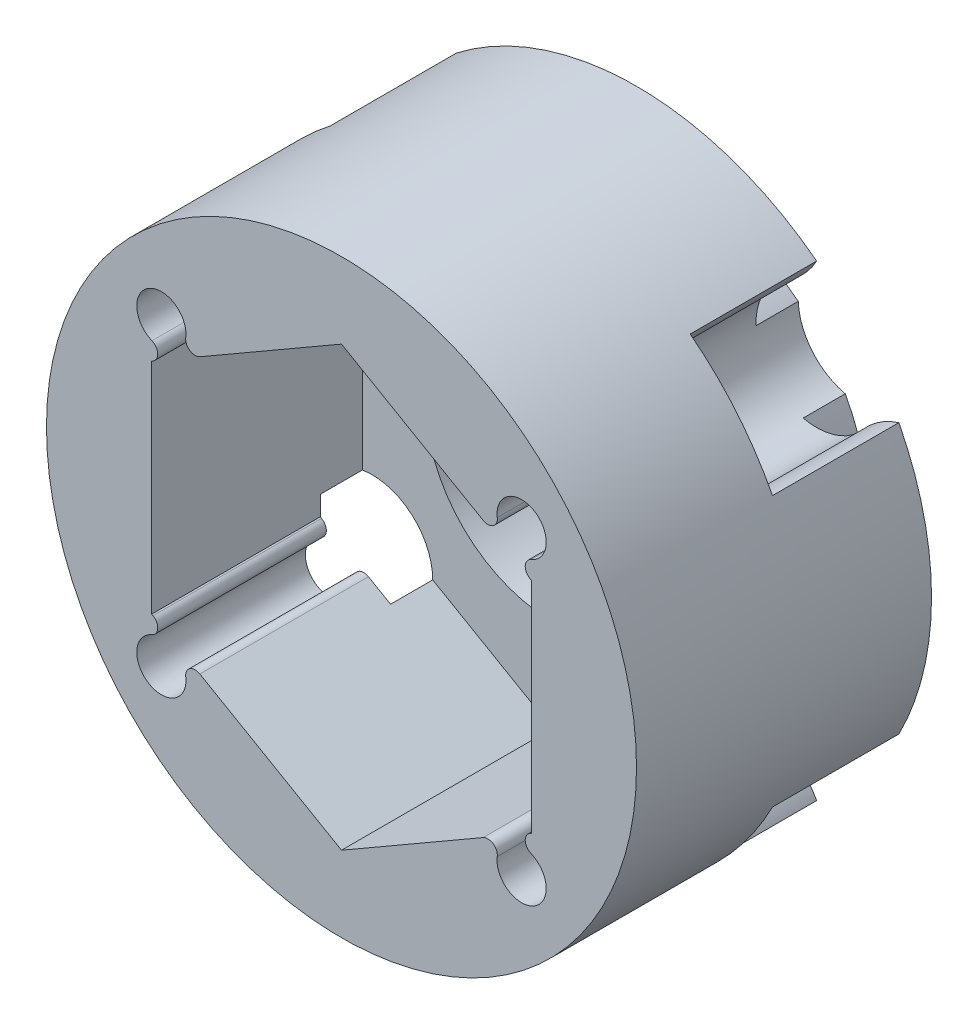
SolidWorks part; units mm, degrees
note: The reader was unsure of these and kept them because the rebuilt part matched: shared geometry of "Sketch4<3>", "Sketch1<5>", "Sketch1<6>", "Sketch4<4>".
material "ABS"
ref_plane "Front Plane" through (0, 0, 0) normal (0, 0, 1) x (1, 0, 0)
ref_plane "Top Plane" through (0, 0, 0) normal (0, 1, 0) x (1, 0, 0)
ref_plane "Right Plane" through (0, 0, 0) normal (1, 0, 0) x (0, 0, -1)
sketch "Sketch1" plane through (0, 0, 0) normal (0, 0, 1) x (1, 0, 0)
  line L0 (0, 8.7454) -> (0, -8.8136) construction
  line L1 (0, -5.2) -> (4.5033, -2.6)
  line L2 (4.5033, -2.6) -> (4.5033, 2.6)
  line L3 (4.5033, 2.6) -> (0, 5.2)
  line L4 (0, 5.2) -> (-4.5033, 2.6)
  line L5 (-4.5033, 2.6) -> (-4.5033, -2.6)
  line L6 (-4.5033, -2.6) -> (0, -5.2)
  line L7 (-10.713, 0) -> (12.0511, 0) construction
  line L8 (0, 0) -> (4.2741, -3.5588) construction
  circle A0 centre (0, 0) radius 7
  circle A1 centre (0, 0) radius 4.5033 construction
  arc A2 (4.4979, 3.0201) -> (3.6956, 3.4833) centre (4.2741, 3.5588) ccw
  arc A3 (3.6956, 3.4833) -> (3.3606, 3.2597) centre (3.4729, 3.4542) cw
  arc A4 (4.4979, 3.0201) -> (4.4718, 2.6182) centre (4.5841, 2.8127) ccw
  arc A5 (-4.4979, 3.0201) -> (-4.4718, 2.6182) centre (-4.5841, 2.8127) cw
  arc A6 (-3.6956, 3.4833) -> (-3.3606, 3.2597) centre (-3.4729, 3.4542) ccw
  arc A7 (-4.4979, 3.0201) -> (-3.6956, 3.4833) centre (-4.2741, 3.5588) cw
  arc A8 (4.4979, -3.0201) -> (4.4718, -2.6182) centre (4.5841, -2.8127) cw
  arc A9 (4.4979, -3.0201) -> (3.6956, -3.4833) centre (4.2741, -3.5588) cw
  arc A10 (3.6956, -3.4833) -> (3.3606, -3.2597) centre (3.4729, -3.4542) ccw
  arc A11 (-3.6956, -3.4833) -> (-3.3606, -3.2597) centre (-3.4729, -3.4542) cw
  arc A12 (-4.4979, -3.0201) -> (-4.4718, -2.6182) centre (-4.5841, -2.8127) ccw
  arc A13 (-4.4979, -3.0201) -> (-3.6956, -3.4833) centre (-4.2741, -3.5588) ccw
  dimension "D2" = 14
  dimension "D1" = 5.2
  dimension "D3" = 3.5588
extrude "Boss-Extrude1" add sketch "Sketch1" against normal blind 7 contours A0 A13 A12 L6 L5 L4 A5 A7 A6 L3 A3 A2 A4 L2 L1 A8 A9 A10 A11 | L5 L6 L1 L2 L3 L4 | A4 A2 A3 L3 | A12 A13 A11 L6 | A10 A9 A8 L1 | A7 A5 L4 A6
sketch "Sketch4" plane through (0, 0, -7) normal (0, 0, -1) x (-1, 0, 0)
  line L0 (0, 8.7454) -> (0, -8.8136) construction
  line L1 (0, 8.7454) -> (0, -8.8136)
  line L2 (10.713, 0) -> (-12.0511, 0) construction
  line L3 (10.713, 0) -> (-12.0511, 0)
  line L4 (-4.2741, 3.5588) -> (-6.1407, 5.113) construction
  circle A0 centre (-4.2741, 3.5588) radius 1.4383
  circle A1 centre (0, 0) radius 7 construction
  circle A2 centre (4.2741, 3.5588) radius 1.4383
  circle A3 centre (4.2741, -3.5588) radius 1.4383
  circle A4 centre (-4.2741, -3.5588) radius 1.4383
  arc A5 (-3.5838, 4.8206) -> (-4.2741, 5.5437) centre (-2.6179, 6.4337) cw
  arc A6 (-5.39, 2.6514) -> (-6.2261, 3.1993) centre (-6.8015, 1.4094) ccw
  arc A7 (5.39, 2.6514) -> (6.2261, 3.1993) centre (6.8015, 1.4094) cw
  arc A8 (3.5838, 4.8206) -> (4.2741, 5.5437) centre (2.6179, 6.4337) ccw
  arc A9 (5.39, -2.6514) -> (6.2261, -3.1993) centre (6.8015, -1.4094) ccw
  arc A10 (3.5838, -4.8206) -> (4.2741, -5.5437) centre (2.6179, -6.4337) cw
  arc A11 (-5.39, -2.6514) -> (-6.2261, -3.1993) centre (-6.8015, -1.4094) cw
  arc A12 (-3.5838, -4.8206) -> (-4.2741, -5.5437) centre (-2.6179, -6.4337) ccw
  circle A13 centre (0, 0) radius 3
  circle A14 centre (0, 0) radius 4.5033
  dimension "D1" = 6
extrude "Boss-Extrude2" add sketch "Sketch4" along normal blind 1 contours L3 A14 A4 L1 A13 | L1 A14 A0 L3 A13 | L3 A14 A2 L1 A13 | L1 A14 A3 L3 A13
extrude "Cut-Extrude4" cut sketch "Sketch4<3>" against normal blind 3
sketch "Sketch4<3>" plane through (0, 0, -7) normal (0, 0, -1) x (-1, 0, 0) same geometry as "Sketch4"
extrude "Cut-Extrude5" cut sketch "Sketch1<5>" against normal blind 5 contours L5 L6 L1 L2 L3 L4
sketch "Sketch1<5>" plane through (0, 0, 0) normal (0, 0, 1) x (1, 0, 0) same geometry as "Sketch1"
extrude "Cut-Extrude6" cut sketch "Sketch1<6>" against normal blind 5 contours A12 A13 A11 L6 | A7 A5 L4 A6 | A4 A2 A3 L3 | A10 A9 A8 L1
sketch "Sketch1<6>" plane through (0, 0, 0) normal (0, 0, 1) x (1, 0, 0) same geometry as "Sketch1"
extrude "Cut-Extrude7" cut sketch "Sketch4<4>" against normal through all both and the other way through all contours L1 A13 L3 | L3 A13 L1 | L1 A13 L3 | L3 A13 L1
sketch "Sketch4<4>" plane through (0, 0, -7) normal (0, 0, -1) x (-1, 0, 0) same geometry as "Sketch4"
